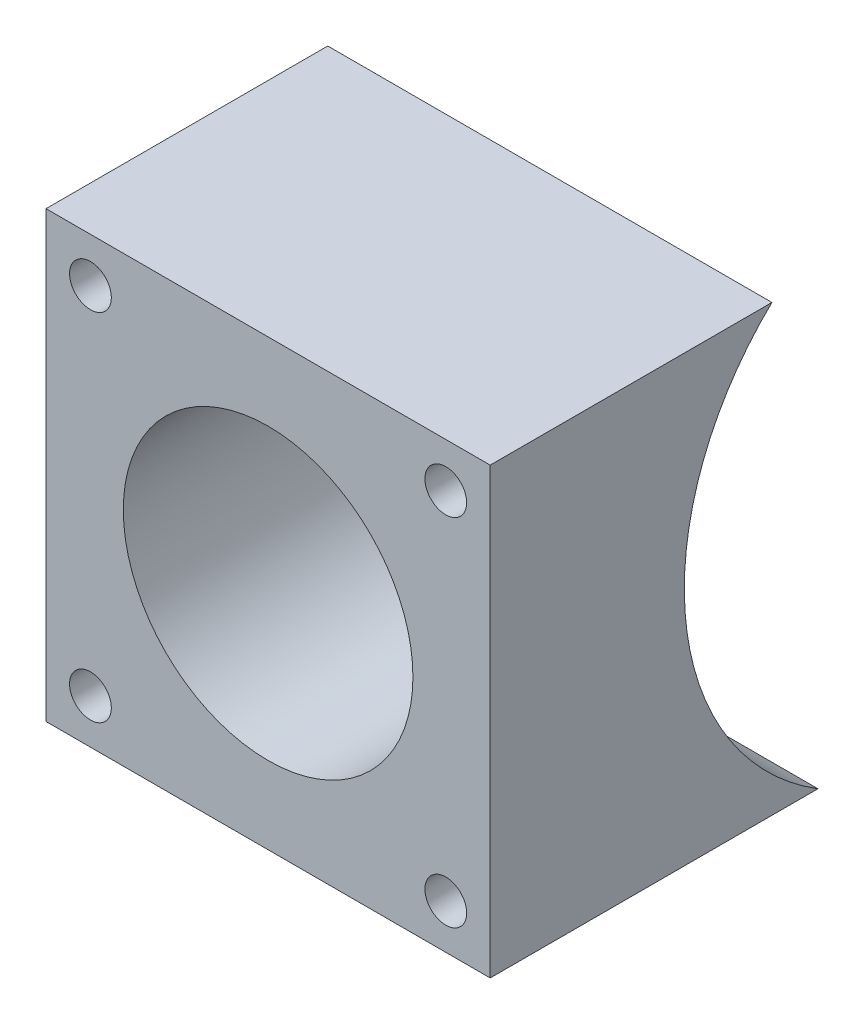
SolidWorks part; units mm, degrees
ref_plane "Front Plane" through (0, 0, 0) normal (0, 0, 1) x (1, 0, 0)
ref_plane "Top Plane" through (0, 0, 0) normal (0, 1, 0) x (1, 0, 0)
ref_plane "Right Plane" through (0, 0, 0) normal (1, 0, 0) x (0, 0, -1)
sketch "Sketch1" plane through (0, 0, 0) normal (0, 0, 1) x (1, 0, 0)
  line L1 (-25, 23) -> (25, 23)
  line L2 (-25, 23) -> (-25, -27)
  line L3 (-25, -27) -> (25, -27)
  line L4 (25, 23) -> (25, -27)
  line L5 (-25, 23) -> (25, -27) construction
  line L6 (-25, -27) -> (25, 23) construction
  circle A0 centre (0, -2) radius 16.3
  circle A1 centre (-20, 18) radius 2.35
  circle A2 centre (20, 18) radius 2.35
  circle A3 centre (20, -22) radius 2.35
  circle A4 centre (-20, -22) radius 2.35
  point P0 (0, -2)
  dimension "D4" = 32.6
  dimension "D6" = 4.7
  dimension "D1" = 2
  dimension "D2" = 50
  dimension "D3" = 50
  dimension "D5" = 20
  dimension "D7" = 20
  dimension "D9" = 20
  dimension "D10" = 20
extrude "Boss-Extrude1" add sketch "Sketch1" along normal blind 53.6
sketch "Sketch2" plane through (0, 0, 0) normal (1, 0, 0) x (0, 0, -1)
  circle A0 centre (0, 0) radius 31.75
  dimension "D1" = 63.5
extrude "Cut-Extrude1" cut sketch "Sketch2" against normal through all and the other way through all
